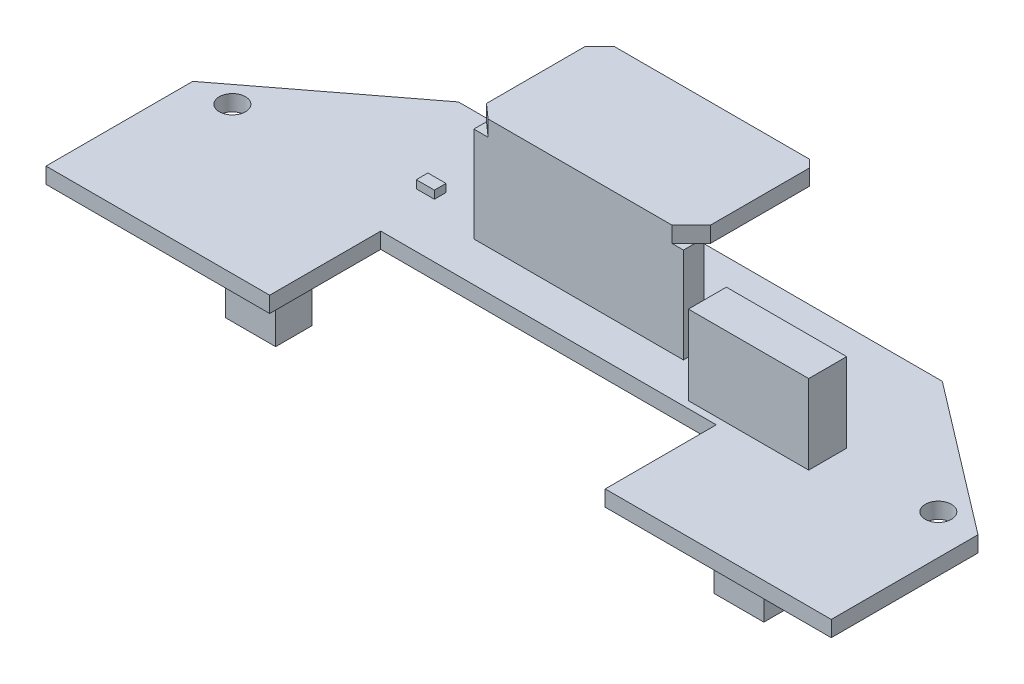
SolidWorks part; units mm, degrees
ref_plane "Plano frontal" through (0, 0, 0) normal (0, 0, 1) x (1, 0, 0)
ref_plane "Plano superior" through (0, 0, 0) normal (0, 1, 0) x (1, 0, 0)
ref_plane "Plano direito" through (0, 0, 0) normal (1, 0, 0) x (0, 0, -1)
sketch "Esboço1" plane through (0, 0, 0) normal (0, 1, 0) x (1, 0, 0)
  line L0 (-49.5, 2) -> (-30.5, 16.5)
  line L1 (-49.5, -16.5) -> (49.5, -16.5) construction
  line L2 (-49.5, -16.5) -> (-49.5, 16.5) construction
  line L3 (-49.5, 16.5) -> (49.5, 16.5) construction
  line L4 (49.5, -16.5) -> (49.5, 16.5) construction
  line L5 (-49.5, -16.5) -> (49.5, 16.5) construction
  line L6 (-49.5, 16.5) -> (49.5, -16.5) construction
  line L7 (30.5, 16.5) -> (49.5, 2)
  line L8 (-21.3, -16.5) -> (-21.3, -2.5)
  line L9 (-21.3, -2.5) -> (21, -2.5)
  line L10 (21, -2.5) -> (21, -16.5)
  line L11 (21, -16.5) -> (49.5, -16.5)
  line L12 (-33.6, -5.15) -> (-27.3, -5.15)
  line L13 (-33.6, -5.15) -> (-33.6, -9.75)
  line L14 (-33.6, -9.75) -> (-27.3, -9.75)
  line L15 (-27.3, -5.15) -> (-27.3, -9.75)
  line L16 (-13.95, 12.55) -> (-7.65, 12.55)
  line L17 (-13.95, 12.55) -> (-13.95, 7.95)
  line L18 (-13.95, 7.95) -> (-7.65, 7.95)
  line L19 (-7.65, 12.55) -> (-7.65, 7.95)
  line L20 (7.05, 12.55) -> (13.35, 12.55)
  line L21 (7.05, 12.55) -> (7.05, 7.95)
  line L22 (7.05, 7.95) -> (13.35, 7.95)
  line L23 (13.35, 12.55) -> (13.35, 7.95)
  line L24 (27.25, -4.45) -> (33.55, -4.45)
  line L25 (27.25, -4.45) -> (27.25, -9.05)
  line L26 (27.25, -9.05) -> (33.55, -9.05)
  line L27 (33.55, -4.45) -> (33.55, -9.05)
  line L28 (49.5, -16.5) -> (49.5, 2)
  line L29 (30.5, 16.5) -> (-30.5, 16.5)
  line L30 (-49.5, 2) -> (-49.5, -16.5)
  line L31 (-49.5, -16.5) -> (-21.3, -16.5)
  circle A0 centre (-44.5, 2) radius 1.65
  circle A1 centre (44.5, 2) radius 1.65
  point P0 (0, 0)
  point P34 (7.05, 10.25)
  point P35 (10.2, 12.55)
  point P36 (-10.8, 12.55)
  point P37 (30.4, -4.45)
  point P38 (27.25, -6.75)
  point P39 (-30.45, -5.15)
  point P40 (-27.3, -7.45)
  dimension "D24" = 3.3
  dimension "D1" = 99
  dimension "D2" = 33
  dimension "D3" = 18.5
  dimension "D4" = 61
  dimension "D5" = 19
  dimension "D6" = 19
  dimension "D7" = 28.2
  dimension "D8" = 28.5
  dimension "D9" = 14
  dimension "D10" = 30.4
  dimension "D11" = 23.25
  dimension "D12" = 30.45
  dimension "D13" = 23.95
  dimension "D18" = 10.8
  dimension "D19" = 6.3
  dimension "D20" = 10.2
  dimension "D21" = 6.25
  dimension "D22" = 4.6
  dimension "D25" = 5
  dimension "D26" = 5
extrude "Ressalto-extrusão1" add sketch "Esboço1" along normal blind 2 contours L0 L29 L7 L28 L11 L10 L9 L8 L31 L30 | A0 | A1
extrude "Ressalto-extrusão2" add sketch "Esboço1<3>" against normal blind 10 contours L13 L14 L15 L12 | L17 L18 L19 L16 | L21 L22 L23 L20 | L25 L26 L27 L24
sketch "Esboço1<3>" plane through (0, 0, 0) normal (0, 1, 0) x (1, 0, 0) same geometry as "Esboço1"
ref_plane "Plano1" through (0, 14, 0) normal (0, 1, 0) x (1, 0, 0)
sketch "Esboço2" plane through (0, 2, 0) normal (0, 1, 0) x (1, 0, 0)
  line L1 (-14.5703, 2.5115) -> (11.8514, 2.5115)
  line L2 (-14.5703, 2.5115) -> (-14.5703, 5.11)
  line L3 (-14.5703, 5.11) -> (11.8514, 5.11)
  line L4 (11.8514, 2.5115) -> (11.8514, 5.11)
extrude "Ressalto-extrusão3" add sketch "Esboço2" along normal up to surface (12 mm away) up to plane "Plano1"
sketch "Esboço3" plane through (0, 14, 0) normal (0, 1, 0) x (1, 0, 0)
  line L0 (-12.7797, 2.5115) -> (10.4008, 2.5115)
  line L1 (-14.5703, 2.5115) -> (11.8514, 2.5115) construction
  line L2 (10.4008, 2.5115) -> (12.8336, 4.9444)
  line L3 (12.8336, 4.9444) -> (12.8336, 17.3961)
  line L4 (12.8336, 17.3961) -> (11.8514, 18.3783)
  line L5 (11.8514, 18.3783) -> (-12.7797, 18.3783)
  line L6 (-12.7797, 18.3783) -> (-14.5703, 16.5877)
  line L7 (-14.5703, 16.5877) -> (-14.5703, 4.1071)
  line L8 (-14.5703, 4.1071) -> (-12.7797, 2.5115)
extrude "Ressalto-extrusão4" add sketch "Esboço3" along normal blind 2
sketch "Esboço4" plane through (0, 2, 0) normal (0, 1, 0) x (1, 0, 0)
  line L1 (16.6098, -1.623) -> (31.778, -1.623)
  line L2 (16.6098, -1.623) -> (16.6098, 3.1674)
  line L3 (16.6098, 3.1674) -> (31.778, 3.1674)
  line L4 (31.778, -1.623) -> (31.778, 3.1674)
extrude "Ressalto-extrusão5" add sketch "Esboço4" along normal blind 10
sketch "Esboço5" plane through (0, 2, 0) normal (0, 1, 0) x (1, 0, 0)
  line L1 (-23.6704, 5.8199) -> (-21.392, 5.8199)
  line L2 (-23.6704, 5.8199) -> (-23.6704, 4.3542)
  line L3 (-23.6704, 4.3542) -> (-21.392, 4.3542)
  line L4 (-21.392, 5.8199) -> (-21.392, 4.3542)
extrude "Ressalto-extrusão6" add sketch "Esboço5" along normal blind 1
